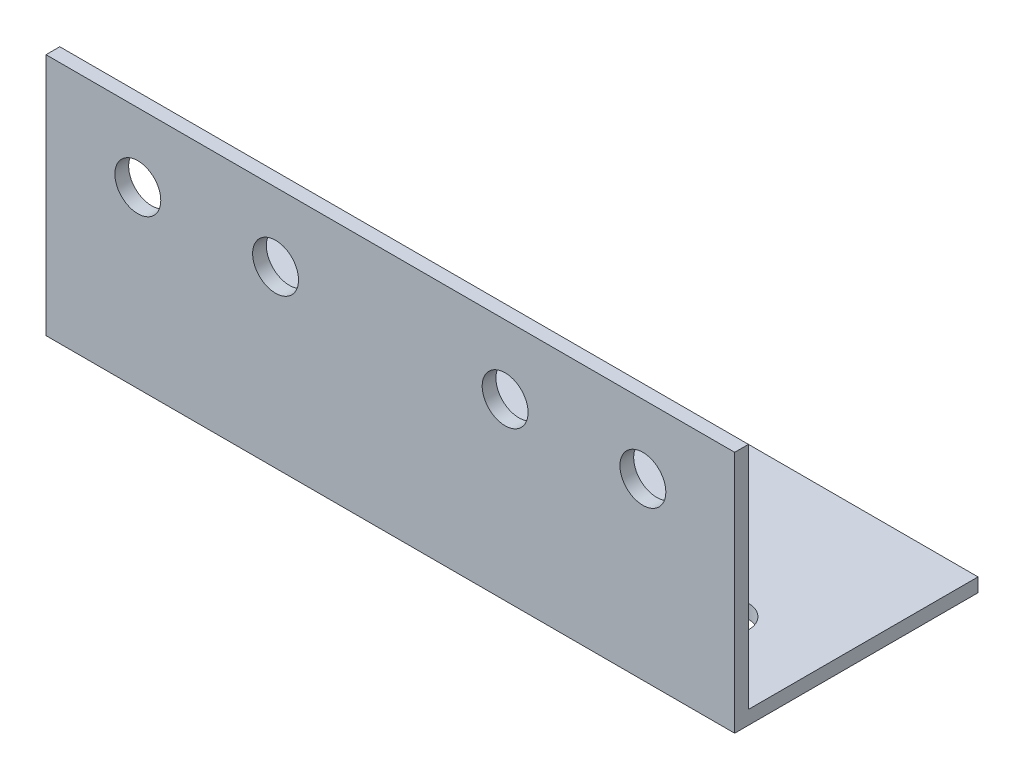
SolidWorks part; units mm, degrees
ref_plane "Спереди" through (0, 0, 0) normal (0, 0, 1) x (1, 0, 0)
ref_plane "Сверху" through (0, 0, 0) normal (0, 1, 0) x (1, 0, 0)
ref_plane "Справа" through (0, 0, 0) normal (1, 0, 0) x (0, 0, -1)
sketch "Эскиз1" plane through (0, 0, 0) normal (1, 0, 0) x (0, 0, -1)
  line L0 (0, 0) -> (0, 50)
  line L1 (0, 0) -> (50, 0)
extrude "Вытянуть-Тонкостенный1" add sketch "Эскиз1" along normal blind 150 thin thin type one direction wall 3
sketch "Эскиз2" plane through (0, 0, 3) normal (0, 0, 1) x (1, 0, 0)
  line L0 (75, 57.1198) -> (75, 24.9932) construction
  circle A0 centre (20, 35) radius 5
  circle A1 centre (50, 35) radius 5
  circle A2 centre (100, 35) radius 5
  circle A3 centre (130, 35) radius 5
  dimension "D1" = 2
extrude "Вырез-Вытянуть1" cut sketch "Эскиз2" against normal through all
sketch "Эскиз3" plane through (0, -3, 0) normal (0, -1, 0) x (1, 0, 0)
  line L0 (75, -55.6806) -> (75, -1.3862) construction
  circle A0 centre (130, -15) radius 5
  circle A1 centre (100, -15) radius 5
  circle A2 centre (50, -15) radius 5
  circle A3 centre (20, -15) radius 5
  dimension "D1" = 2
extrude "Вырез-Вытянуть2" cut sketch "Эскиз3" against normal through all
